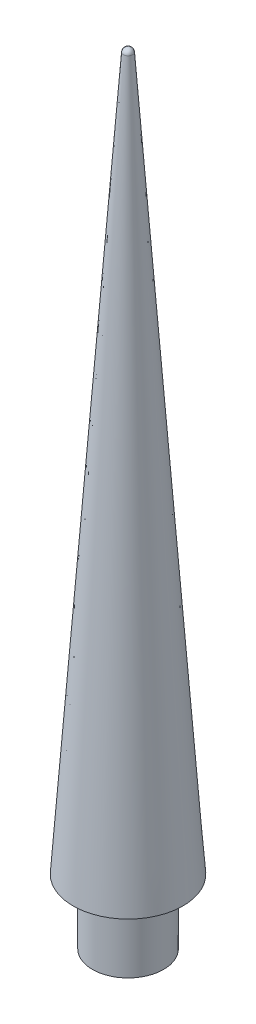
SolidWorks part; units mm, degrees
material "6061-T6 (SS)"
ref_plane "Front Plane" through (0, 0, 0) normal (0, 0, 1) x (1, 0, 0)
ref_plane "Top Plane" through (0, 0, 0) normal (0, 1, 0) x (1, 0, 0)
ref_plane "Right Plane" through (0, 0, 0) normal (1, 0, 0) x (0, 0, -1)
sketch "Sketch2" plane through (0, 0, 0) normal (0, 0, 1) x (1, 0, 0)
  line L0 (0, 0) -> (0, 152.4) construction
  line L1 (0, 0) -> (-10.795, 0)
  line L2 (-10.795, 0) -> (0, 152.4) construction
  line L3 (0, 152.4) -> (0, 0) construction
  line L4 (-10.795, 0) -> (-0.8996, 139.7)
  line L5 (0, 0) -> (0, 140.5381)
  arc A0 (-0.8996, 139.7) -> (0, 140.5381) centre (0, 139.6363) cw
  point P7 (-0.0744, 138.2764)
  point P8 (0, 0)
  dimension "D1" = 152.4
  dimension "D2" = 10.795
  dimension "D3" = 12.7
revolve "Revolve1" add sketch "Sketch2" angle 360 about L0
sketch "Sketch5" plane through (0, 0, 0) normal (0, -1, 0) x (1, 0, 0)
  circle A0 centre (0, 0) radius 6.985
  dimension "D1" = 13.97
extrude "Boss-Extrude1" add sketch "Sketch5" along normal blind 12.7
hole_wizard "1/4 (0.25) Diameter Hole1" positions "Sketch6" profile "Sketch7" hole size "1/4" standard "ANSI Inch"
sketch "Sketch6" plane through (0, -12.7, 0) normal (0, -1, 0) x (1, 0, 0)
  point P0 (0, 0)
  point P3 (0, 0)
sketch "Sketch7" plane through (0, -12.7, 0) normal (1, 0, 0) x (0, 0, -1)
  line L0 (0, 0) -> (0, 40.0077)
  line L1 (0, 40.0077) -> (3.175, 38.1)
  line L2 (3.175, 38.1) -> (3.175, 0.635)
  line L3 (3.175, 0.635) -> (3.81, 0)
  line L5 (3.81, 0) -> (0, 0)
  line L6 (-3.175, 0.635) -> (-3.81, 0) construction
  line L10 (0, 40.0077) -> (-3.175, 38.1) construction
  line L11 (0, -6.35) -> (0, 107.95) construction
  dimension "Hole Dia." = 6.35
  dimension "Hole Depth" = 38.1
  dimension "Near C'Sink Dia." = 7.62
  dimension "Near C'Sink Angle" = 90
  dimension "Drill Angle" = 118
thread "Thread1" pitch 1.27 method extrude profile "Thread Profile2" start angle 0, offset 0, length 25.4, pitch 1.27, diameter 6.35
ref_plane "Plane2" through (3.175, -12.065, 0) normal (0, 0, 1) x (1, 0, 0)
sketch "Thread Profile2" plane through (3.175, -12.065, 0) normal (0, 0, 1) x (1, 0, 0)
  line L0 (0, 0) -> (0, 1.27) construction
  line L11 (0, 0) -> (0, 1.1112)
  line L12 (0, 1.1112) -> (-0.6874, 0.7144)
  line L13 (-0.6874, 0.7144) -> (-0.6874, 0.3969)
  line L15 (-0.6874, 0.3969) -> (0, 0)
  line L17 (-0.6874, 0.5556) -> (0, 0.5556) construction
  point P2 (0, 0)
  dimension "Pitch" = 1.27
  dimension "Profile_Angle" = 60
  dimension "Profile_Land" = 0.3175
  dimension "Profile_Height" = 0.6874
